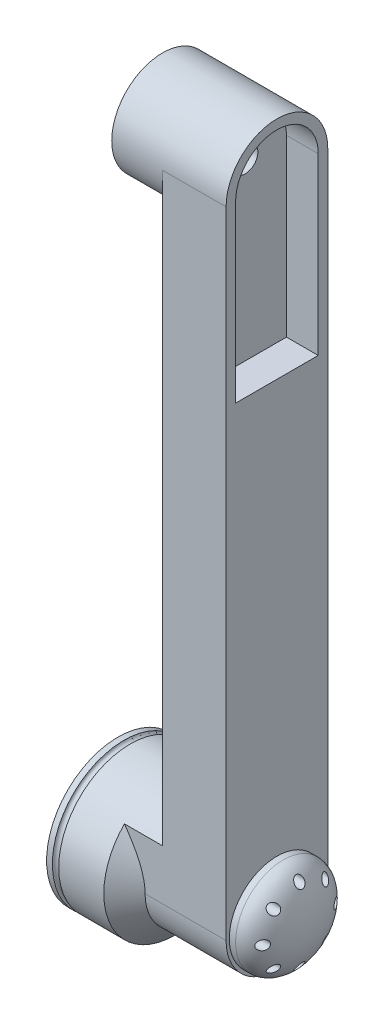
SolidWorks part; units mm, degrees
ref_plane "Front Plane" through (0, 0, 0) normal (0, 0, 1) x (1, 0, 0)
ref_plane "Top Plane" through (0, 0, 0) normal (0, 1, 0) x (1, 0, 0)
ref_plane "Right Plane" through (0, 0, 0) normal (1, 0, 0) x (0, 0, -1)
sketch "Sketch2" plane through (0, 0, 0) normal (1, 0, 0) x (0, 0, -1)
  circle A0 centre (0, 0) radius 22.5
  dimension "D1" = 45
extrude "Boss-Extrude1" add sketch "Sketch2" along normal blind 30 contours A0
sketch "Sketch3" plane through (30, 0, 0) normal (1, 0, 0) x (0, 0, -1)
  line L0 (0, 0) -> (0, 200) construction
  line L1 (-16, 0) -> (-16, 200)
  line L2 (16, 0) -> (16, 200)
  arc A0 (-16, 0) -> (16, 0) centre (0, 0) ccw
  arc A1 (16, 200) -> (-16, 200) centre (0, 200) ccw
  point P3 (0, 100)
extrude "Boss-Extrude2" add sketch "Sketch3" along normal blind 20
chamfer "Chamfer1" distance 12 angle 45 1 edges at (30, -22.5, 0)
sketch "Sketch8" plane through (0, 0, 0) normal (-1, 0, 0) x (0, 0, 1)
  circle A0 centre (0, 0) radius 3
extrude "Cut-Extrude4" cut sketch "Sketch8" against normal blind 50
sketch "Sketch9" plane through (50, 0, 0) normal (1, 0, 0) x (0, 0, -1)
  circle A0 centre (0, 0) radius 15
  circle A1 centre (0, 11.4425) radius 1.5
  circle A2 centre (8.0911, 8.0911) radius 1.5
  circle A3 centre (11.4425, 0) radius 1.5
  circle A4 centre (8.0911, -8.0911) radius 1.5
  circle A5 centre (0, -11.4425) radius 1.5
  circle A6 centre (-8.0911, -8.0911) radius 1.5
  circle A7 centre (-11.4425, 0) radius 1.5
  circle A8 centre (-8.0911, 8.0911) radius 1.5
  point P21 (0, 0)
  dimension "D1" = 8
sketch "Sketch12" plane through (50, 0, 0) normal (1, 0, 0) x (0, 0, -1)
  line L0 (-13, 200) -> (-13, 145)
  line L1 (-13, 145) -> (13, 145)
  line L2 (13, 145) -> (13, 200)
  arc A0 (13, 200) -> (-13, 200) centre (0, 200) ccw
extrude "Cut-Extrude5" cut sketch "Sketch12" against normal blind 10
extrude "Boss-Extrude3" add sketch "Sketch9" along normal blind 2 contours A0
dome "Dome1" faces to dome 1 distance 8 reverse direction no elliptical dome yes face at (52, 0, -15) parameters "D1"=8
sketch "Sketch13" plane through (50, 0, 0) normal (1, 0, 0) x (0, 0, -1)
  circle A0 centre (0, 11.4814) radius 1.5
  circle A1 centre (8.1186, 8.1186) radius 1.5
  circle A2 centre (11.4814, 0) radius 1.5
  circle A3 centre (8.1186, -8.1186) radius 1.5
  circle A4 centre (0, -11.4814) radius 1.5
  circle A5 centre (-8.1186, -8.1186) radius 1.5
  circle A6 centre (-11.4814, 0) radius 1.5
  circle A7 centre (-8.1186, 8.1186) radius 1.5
  point P19 (0, 0)
  dimension "D1" = 8
extrude "Cut-Extrude6" cut sketch "Sketch13" along normal through all from surface starting at face at (50, 0, -15)
sketch "Sketch14" plane through (0, 0, 0) normal (0, 0, 1) x (1, 0, 0)
  line L0 (30, 22.5) -> (0, 22.5) construction
  line L1 (0, 0) -> (-7.6829, 0) construction
  circle A0 centre (2.8188, 22.5) radius 1
revolve "Cut-Revolve1" cut sketch "Sketch14" angle 360 about L1
sketch "Sketch15" plane through (30, 0, 0) normal (-1, 0, 0) x (0, 0, 1)
  circle A0 centre (0, 200) radius 16
extrude "Boss-Extrude5" add sketch "Sketch15" along normal blind 16
sketch "Sketch16" plane through (14, 0, 0) normal (-1, 0, 0) x (0, 0, 1)
  circle A0 centre (0, 200) radius 14
extrude "Cut-Extrude7" cut sketch "Sketch16" against normal blind 20
sketch "Sketch17" plane through (34, 0, 0) normal (-1, 0, 0) x (0, 0, 1)
  circle A0 centre (0, 200) radius 4
extrude "Cut-Extrude8" cut sketch "Sketch17" against normal blind 2
sketch "Sketch18" plane through (40, 0, 0) normal (1, 0, 0) x (0, 0, -1)
  circle A0 centre (0, 200) radius 4
extrude "Cut-Extrude9" cut sketch "Sketch18" against normal blind 2
sketch "Sketch19" plane through (36, 0, 0) normal (-1, 0, 0) x (0, 0, 1)
  circle A0 centre (0, 200) radius 3
extrude "Cut-Extrude10" cut sketch "Sketch19" against normal through all
